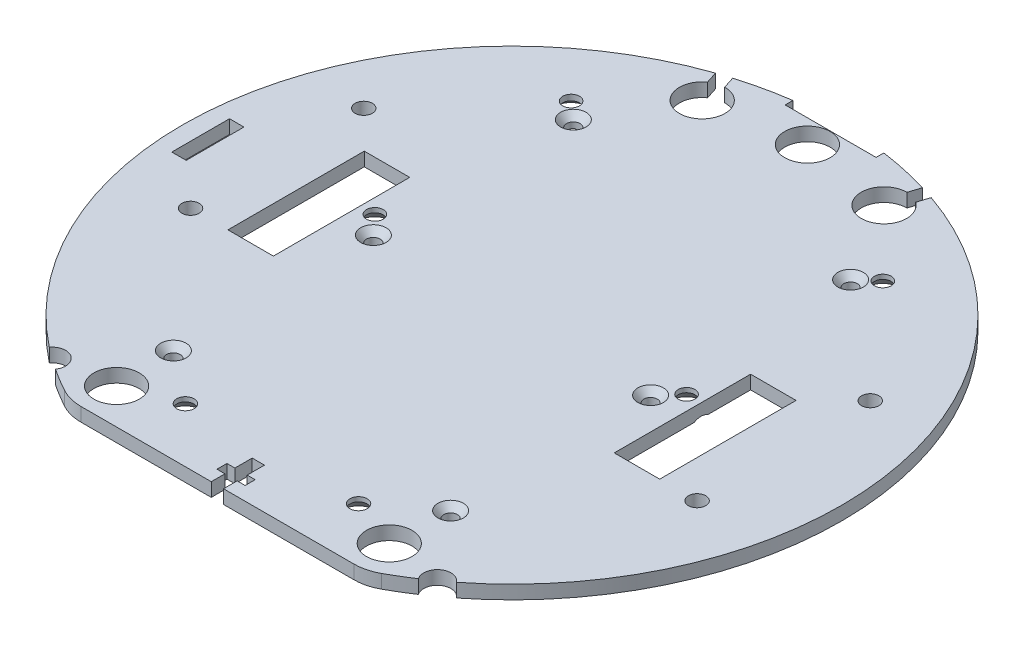
SolidWorks part; units mm, degrees
material "Acrylic (Medium-high impact)"
ref_plane "Front Plane" through (0, 0, 0) normal (0, 0, 1) x (1, 0, 0)
ref_plane "Top Plane" through (0, 0, 0) normal (0, 1, 0) x (1, 0, 0)
ref_plane "Right Plane" through (0, 0, 0) normal (1, 0, 0) x (0, 0, -1)
sketch "Sketch1" plane through (0, 0, 0) normal (0, 1, 0) x (1, 0, 0)
  line L0 (0, -85) -> (0, 0) construction
  line L1 (30.03, -64.8129) -> (-30.03, -64.8129)
  line L3 (-65.325, 6.35) -> (-68.5, 6.35)
  line L4 (-65.325, 6.35) -> (-65.325, -6.35)
  line L5 (-65.325, -6.35) -> (-68.5, -6.35)
  line L6 (-68.5, 6.35) -> (-68.5, -6.35)
  arc A0 (34.8348, -63.5829) -> (-34.8348, -63.5829) centre (0, 0) ccw
  circle A1 centre (0, -85) radius 38.25 construction
  arc A2 (30.03, -64.8129) -> (34.8348, -63.5829) centre (30.03, -54.8129) ccw
  arc A3 (-30.03, -64.8129) -> (-34.8348, -63.5829) centre (-30.03, -54.8129) cw
  point P12 (-32.4891, -64.8129)
  point P15 (-65.325, 0)
  point P16 (-72.5, 0)
  point P17 (-68.5, 0)
  dimension "D1" = 145
  dimension "D3" = 76.5
  dimension "D4" = 10
  dimension "D2" = 85
  dimension "D5" = 3.175
  dimension "D6" = 12.7
  dimension "D7" = 4
extrude "Boss-Extrude1" add sketch "Sketch1" along normal blind 3
sketch "Sketch2" plane through (0, 3, 0) normal (0, 1, 0) x (1, 0, 0)
  line L1 (-30.5, -44) -> (30.5, -44) construction
  line L2 (-30.5, -44) -> (-30.5, 44) construction
  line L3 (-30.5, 44) -> (30.5, 44) construction
  line L4 (30.5, -44) -> (30.5, 44) construction
  line L5 (-30.5, -44) -> (30.5, 44) construction
  line L6 (-30.5, 44) -> (30.5, -44) construction
  circle A0 centre (-30.5, 44) radius 1.5
  circle A1 centre (30.5, 44) radius 1.5
  circle A2 centre (30.5, 0) radius 1.5
  circle A3 centre (30.5, -44) radius 1.5
  circle A4 centre (-30.5, -44) radius 1.5
  circle A5 centre (-30.5, 0) radius 1.5
  point P0 (0, 0)
  dimension "D3" = 3
  dimension "D1" = 61
  dimension "D2" = 88
extrude "Cut-Extrude1" cut sketch "Sketch2" against normal through all
chamfer "Chamfer1" distance 1.5 angle 41 6 edges at (30.5, 3, -42.5) (30.5, 3, 1.5) (30.5, 3, 45.5) (-30.5, 3, 45.5) (-30.5, 3, 1.5) (-30.5, 3, -42.5)
sketch "Sketch3" plane through (0, 3, 0) normal (0, 1, 0) x (1, 0, 0)
  line L0 (-30.03, -64.8129) -> (30.03, -64.8129) construction
  line L1 (1.35, -61.8129) -> (3.1, -61.8129)
  line L2 (-3.1, -59.6129) -> (-1.35, -59.6129)
  line L3 (-3.1, -59.6129) -> (-3.1, -61.8129)
  line L4 (-3.1, -61.8129) -> (-1.35, -61.8129)
  line L5 (3.1, -59.6129) -> (3.1, -61.8129)
  line L6 (-1.35, -64.8129) -> (1.35, -64.8129)
  line L7 (-1.35, -64.8129) -> (-1.35, -61.8129)
  line L8 (1.35, -59.6129) -> (3.1, -59.6129)
  line L9 (1.35, -64.8129) -> (1.35, -61.8129)
  line L11 (-1.35, -59.6129) -> (-1.35, -55.8129)
  line L12 (-1.35, -55.8129) -> (1.35, -55.8129)
  line L13 (1.35, -59.6129) -> (1.35, -55.8129)
  point P10 (0, -64.8129)
  point P14 (0, -64.8129)
  dimension "D1" = 2.7
  dimension "D2" = 6.2
  dimension "D3" = 2.2
  dimension "D4" = 3
  dimension "D5" = 9
extrude "Cut-Extrude2" cut sketch "Sketch3" against normal through all
sketch "Sketch4" plane through (0, 3, 0) normal (0, 1, 0) x (1, 0, 0)
  line L1 (-10, 71.807) -> (10, 71.807)
  line L2 (-10, 71.807) -> (-10, 70.107)
  line L3 (-10, 70.107) -> (10, 70.107)
  line L4 (10, 71.807) -> (10, 70.107)
  arc A0 (34.8348, -63.5829) -> (-34.8348, -63.5829) centre (0, 0) ccw construction
  dimension "D1" = 1.7
  dimension "D2" = 20
extrude "Cut-Extrude3" cut sketch "Sketch4" against normal through all
sketch "Sketch5" plane through (0, 3, 0) normal (0, 1, 0) x (1, 0, 0)
  line L0 (0, 0) -> (0, 65) construction
  circle A0 centre (0, 65) radius 5
  circle A1 centre (30, -57) radius 5
  circle A2 centre (-30, -57) radius 5
  dimension "D1" = 10
  dimension "D2" = 65
  dimension "D3" = 57
  dimension "D4" = 30
extrude "Cut-Extrude4" cut sketch "Sketch5" against normal through all
sketch "Sketch6" plane through (0, 3, 0) normal (0, 1, 0) x (1, 0, 0)
  line L0 (38.1, 0.307) -> (38.1, 51.107) construction
  line L1 (-34.29, 4.117) -> (34.29, 4.117) construction
  line L2 (-34.29, 4.117) -> (-34.29, 47.297) construction
  line L3 (-34.29, 47.297) -> (34.29, 47.297) construction
  line L4 (34.29, 4.117) -> (34.29, 47.297) construction
  line L5 (-38.1, 51.107) -> (38.1, 51.107) construction
  line L6 (-38.1, 0.307) -> (-38.1, 51.107) construction
  line L7 (-38.1, 0.307) -> (38.1, 0.307) construction
  line L8 (-10, 70.107) -> (10, 70.107) construction
  circle A0 centre (-34.29, 47.297) radius 1.8415
  circle A1 centre (-34.29, 4.117) radius 1.8415
  circle A2 centre (34.29, 4.117) radius 1.8415
  circle A3 centre (34.29, 47.297) radius 1.8415
  arc A5 (-10, 71.807) -> (-34.8348, -63.5829) centre (0, 0) ccw construction
  point P13 (-38.1, 25.707)
  point P14 (0, 0)
  point P17 (-67.7894, 25.707)
  point P18 (0, 4.117)
  dimension "D3" = 3.683
  dimension "D1" = 68.58
  dimension "D2" = 43.18
  dimension "D5" = 19
  dimension "D4" = 3.81
extrude "Cut-Extrude5" cut sketch "Sketch6" against normal through all
sketch "Sketch8" plane through (0, 3, 0) normal (0, 1, 0) x (1, 0, 0)
  line L0 (1.35, -64.8129) -> (30.03, -64.8129) construction
  line L1 (-20, 61.8466) -> (20, 61.8466) construction
  line L2 (-10, 70.107) -> (10, 70.107) construction
  line L3 (-37.5, 0) -> (37.5, 0) construction
  line L4 (-47.5, 15) -> (-37.5, 15)
  line L5 (-47.5, 15) -> (-47.5, -15)
  line L6 (-47.5, -15) -> (-37.5, -15)
  line L7 (-37.5, 15) -> (-37.5, -15)
  line L8 (37.5, 15) -> (47.5, 15)
  line L9 (37.5, 15) -> (37.5, -15)
  line L10 (37.5, -15) -> (47.5, -15)
  line L11 (47.5, 15) -> (47.5, -15)
  line L12 (-23.7301, 68.5064) -> (-22.8948, 65.9233)
  line L13 (-22.3029, 68.968) -> (-20, 61.8466) construction
  line L14 (-20.0404, 66.8464) -> (-20.8757, 69.4295)
  line L15 (20.0404, 66.8464) -> (20.8757, 69.4295)
  line L16 (22.3077, 68.9827) -> (20, 61.8466) construction
  line L17 (22.8948, 65.9233) -> (23.7301, 68.5064)
  line L18 (22.8948, 65.9233) -> (20.0404, 66.8464) construction
  line L19 (-22.8948, 65.9233) -> (-20.0404, 66.8464) construction
  line L20 (19.05, -52.8129) -> (-19.05, -52.8129) construction
  line L21 (-30.03, -64.8129) -> (-1.35, -64.8129) construction
  line L22 (-55.7215, -15) -> (-70.9313, -15) construction
  line L23 (55.7215, -15) -> (70.9313, -15) construction
  arc A0 (39.9251, -60.5164) -> (44.7914, -57.0086) centre (42.3945, -58.8129) cw
  arc A1 (34.8348, -63.5829) -> (10, 71.807) centre (0, 0) ccw construction
  arc A2 (39.9251, -60.5164) -> (44.7914, -57.0086) centre (0, 0) ccw
  arc A3 (-39.9251, -60.5164) -> (-44.7914, -57.0086) centre (-42.3945, -58.8129) ccw
  arc A4 (-10, 71.807) -> (-34.8348, -63.5829) centre (0, 0) ccw construction
  arc A5 (-44.7914, -57.0086) -> (-39.9251, -60.5164) centre (0, 0) ccw
  circle A6 centre (55.7215, -15) radius 1.905
  circle A7 centre (-20, 61.8466) radius 5 construction
  circle A8 centre (20, 61.8466) radius 5 construction
  circle A9 centre (0, 65) radius 5 construction
  arc A10 (-20, 61.8466) -> (20, 61.8466) centre (0, 0) cw construction
  arc A11 (-23.7301, 68.5064) -> (-20.8757, 69.4295) centre (-22.3029, 68.968) cw
  arc A12 (-22.8948, 65.9233) -> (-20.0404, 66.8464) centre (-20, 61.8466) ccw
  arc A13 (20.0404, 66.8464) -> (22.8948, 65.9233) centre (20, 61.8466) ccw
  arc A14 (20.8757, 69.4295) -> (23.7301, 68.5064) centre (22.3029, 68.968) cw
  circle A15 centre (55.7215, 23.1) radius 1.905
  circle A16 centre (19.05, -52.8129) radius 1.905
  circle A17 centre (-19.05, -52.8129) radius 1.905
  circle A18 centre (-55.7215, 23.1) radius 1.905
  circle A19 centre (-55.7215, -15) radius 1.905
  point P7 (40.6403, -56.3792)
  point P11 (0, 61.8466)
  point P12 (42.3945, -58.8129)
  point P24 (0, 70.107)
  point P27 (0, 65)
  point P37 (47.5, 0)
  point P38 (-37.5, 0)
  point P39 (37.5, 0)
  point P41 (0, 0)
  point P56 (21.4676, 66.3849)
  point P63 (0, -52.8129)
  point P65 (68.7215, 23.1)
  dimension "D8" = 3.81
  dimension "D12" = 3.81
  dimension "D1" = 3
  dimension "D2" = 6
  dimension "D3" = 40
  dimension "D4" = 10
  dimension "D5" = 30
  dimension "D6" = 75
  dimension "D7" = 3
  dimension "D9" = 38.1
  dimension "D10" = 13
  dimension "D11" = 38.1
  dimension "D13" = 12
extrude "Cut-Extrude7" cut sketch "Sketch8" against normal through all
chamfer "Chamfer2" distance 2 angle 41 6 edges at (-34.29, 0, -45.4555) (34.29, 0, -45.4555) (34.29, 0, -2.2755) (-34.29, 0, -2.2755) (-19.05, 0, 54.7179) (19.05, 0, 54.7179)
equation "\"smallPulleyTeeth\"= 30"
equation "\"largePulleyTeeth\"= 30"
equation "\"eighthThick\"= 3.0mm"
equation "\"sixteenthThick\"= 1.7mm"
equation "\"quarterThick\"=6.0mm"
equation "\"OD\"= 145mm"
equation "\"puckAngle\"= 60.5deg"
equation "\"puckDiam\"= 76.5mm"
equation "\"puckDist\"= 85mm"
equation "\"scoopFillet\"= 5mm"
equation "\"axlePress\"= 5.9mm"
equation "\"press\"= 0.2mm"
equation "\"wheelClear\"= 0.3mm"
equation "\"10-32clear\"= 4.8mm"
equation "\"10-32tap\"= 4.45mm"
equation "\"6-32clear\"= 3.3mm"
equation "\"8-32clear\"= 4.0mm"
equation "\"4-40clear\"= 3.0mm"
equation "\"wheelHeight\"= 22mm"
equation "\"wheelWell\"= 65mm"
equation "\"ledSmall\"= 3.1mm"
equation "\"ledLarge\"= 4.2mm"
equation "\"ledLength\"= 4.2mm"
equation "\"D1@Sketch1\"=\"OD\""
equation "\"D1@Boss-Extrude1\"=\"eighthThick\""
equation "\"D3@Sketch2\"=\"4-40clear\""
equation "\"D3@Sketch1\"=\"puckDiam\""
equation "\"D2@Sketch1\"=\"puckDist\""
equation "\"4-40close\"= 2.7mm"
equation "\"4-40nutThick\"= 2.2mm"
equation "\"4-40nutWidth\"= 6.2mm"
equation "\"D1@Sketch4\"=\"sixteenthThick\""
equation "\"D1@Sketch3\"=\"4-40close\""
equation "\"4-40insertHeight\"= 3.5mm"
equation "\"4-40insert\"= 4.25mm"
equation "\"D2@Sketch3\"=\"4-40nutWidth\""
equation "\"D3@Sketch3\"=\"4-40nutThick\""
